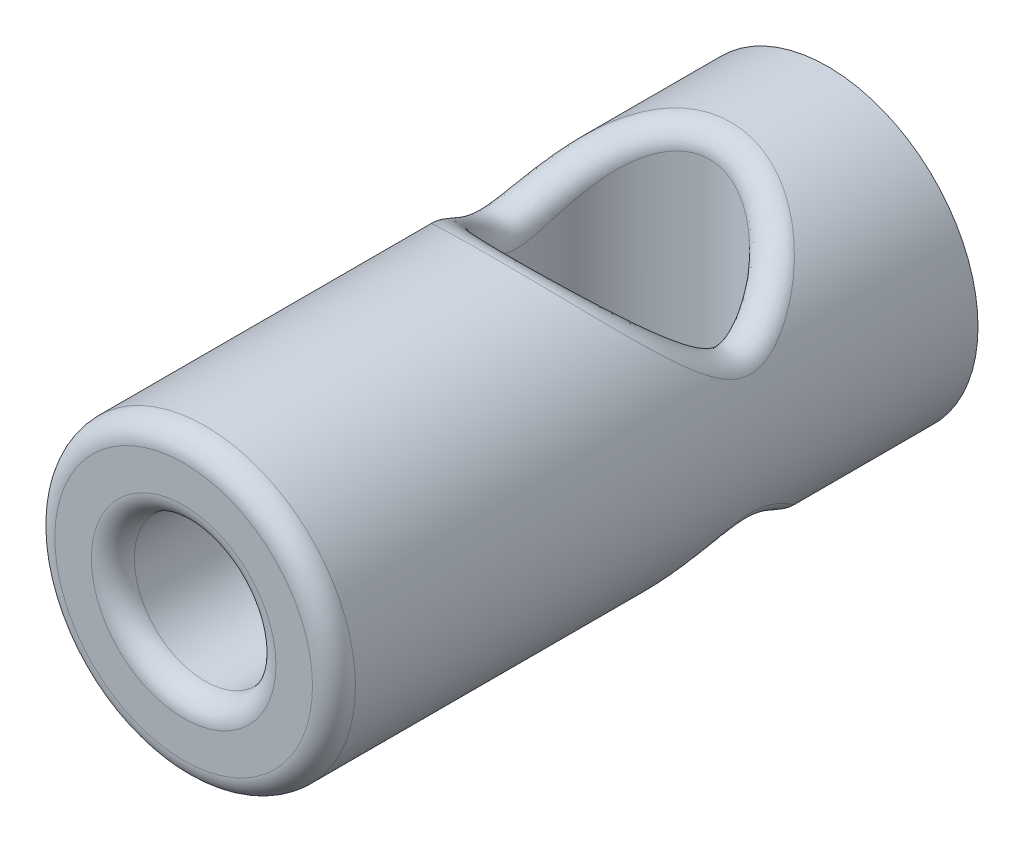
SolidWorks part; units mm, degrees
ref_plane "前视基准面" through (0, 0, 0) normal (0, 0, 1) x (1, 0, 0)
ref_plane "上视基准面" through (0, 0, 0) normal (0, 1, 0) x (1, 0, 0)
ref_plane "右视基准面" through (0, 0, 0) normal (1, 0, 0) x (0, 0, -1)
sketch "草图1" plane through (0, 0, 0) normal (0, 0, 1) x (1, 0, 0)
  circle A0 centre (0, 0) radius 3.5
  dimension "D1" = 7
extrude "凸台-拉伸1" add sketch "草图1" along normal blind 15
hole_wizard "M4x0.7 螺纹孔1" positions "草图3" profile "草图2" tap size "M4x0.7" standard "Ansi Metric"
sketch "草图3" plane through (0, 0, 15) normal (0, 0, 1) x (1, 0, 0)
  point P0 (0, 0)
sketch "草图2" plane through (0, 0, 15) normal (1, 0, 0) x (0, -1, 0)
  line L0 (0, 0) -> (0, 9.9914)
  line L1 (0, 9.9914) -> (1.65, 9)
  line L2 (1.65, 9) -> (1.65, 0)
  line L5 (1.65, 0) -> (0, 0)
  line L10 (0, 9.9914) -> (-1.65, 9) construction
  line L11 (0, -6.35) -> (0, 107.95) construction
  dimension "螺纹孔钻头直径" = 3.3
  dimension "螺纹孔钻头深度" = 9
  dimension "导头角度" = 118
cosmetic thread "孔螺蚊线1" parameters "D1"=8, "D2"=4
sketch "草图4" plane through (0, 0, 0) normal (0, 1, 0) x (1, 0, 0)
  line L0 (-3.5, -15) -> (3.5, -15) construction
  circle A0 centre (0, -5) radius 2.25
  dimension "D2" = 4.5
  dimension "D1" = 10
extrude "切除-拉伸1" cut sketch "草图4" against normal mid plane 20
fillet "圆角1" radius 0.5 2 edges at (1.65, 0, 15) (3.5, 0, 15)
fillet "圆角2" radius 0.5 3 edges at (-0.3804, -3.4793, 2.7824) (0.3804, 3.4793, 2.7824) (-1.6485, 0.0709, 6.5313)
